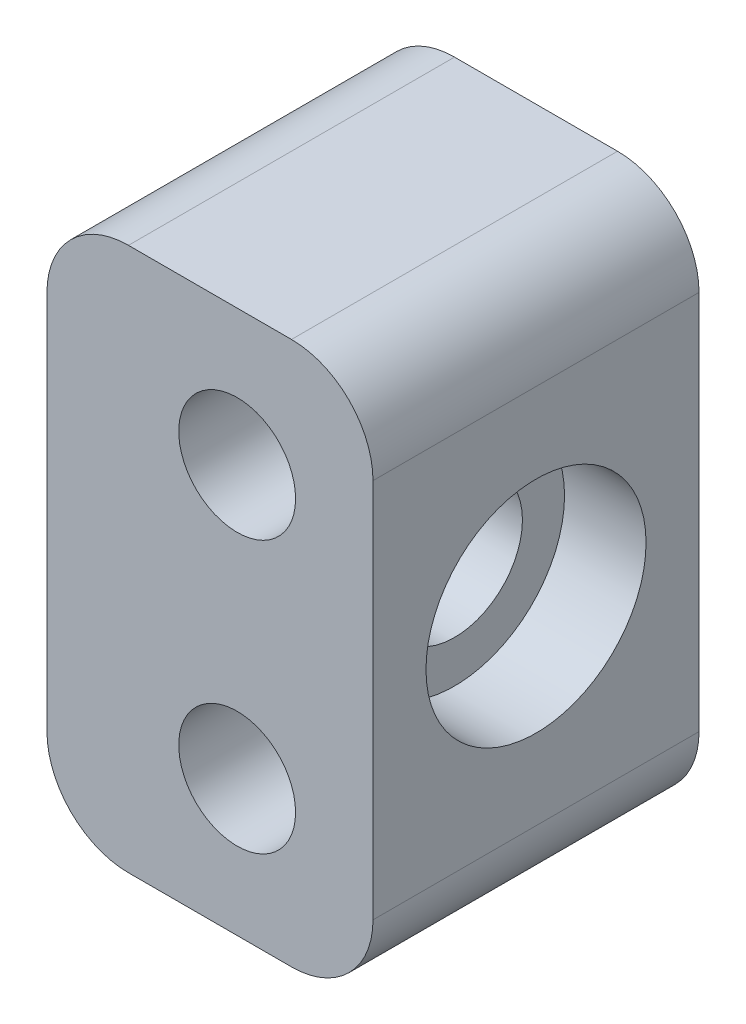
SolidWorks part; units mm, degrees
ref_plane "Front Plane" through (0, 0, 0) normal (0, 0, 1) x (1, 0, 0)
ref_plane "Top Plane" through (0, 0, 0) normal (0, 1, 0) x (1, 0, 0)
ref_plane "Right Plane" through (0, 0, 0) normal (1, 0, 0) x (0, 0, -1)
sketch "Sketch1" plane through (0, 0, 0) normal (0, 0, 1) x (1, 0, 0)
  line L0 (0, 5) -> (0, -5) construction
  line L5 (0, 5) -> (5, 5) construction
  line L6 (-4, -10) -> (2, -10)
  line L7 (-7, -7) -> (-7, 7)
  line L8 (-4, 10) -> (2, 10)
  line L9 (5, -7) -> (5, 7)
  line L10 (-7, -10) -> (5, 10) construction
  line L11 (-7, 10) -> (5, -10) construction
  line L12 (0, 5) -> (0, 10) construction
  circle A2 centre (0, 5) radius 2.15
  circle A3 centre (0, -5) radius 2.15
  arc A4 (-7, -7) -> (-4, -10) centre (-4, -7) ccw
  arc A5 (2, -10) -> (5, -7) centre (2, -7) ccw
  arc A6 (5, 7) -> (2, 10) centre (2, 7) ccw
  arc A7 (-4, 10) -> (-7, 7) centre (-4, 7) ccw
  point P0 (0, 0)
  point P10 (-1, 0)
  dimension "D2" = 10
  dimension "D3" = 4.3
  dimension "D4" = 4.3
  dimension "D6" = 3
  dimension "D1" = 12
  dimension "D5" = 20
extrude "Boss-Extrude1" add sketch "Sketch1" along normal blind 12
sketch "Sketch2" plane through (-7, 0, 0) normal (-1, 0, 0) x (0, 0, 1)
  line L0 (0, 0) -> (12, 0) construction
  line L3 (12, 7) -> (12, -7) construction
  line L10 (2.25, -3.75) -> (9.75, -3.75)
  line L11 (2.25, -3.75) -> (2.25, 3.75)
  line L12 (2.25, 3.75) -> (9.75, 3.75)
  line L13 (9.75, -3.75) -> (9.75, 3.75)
  line L14 (2.25, -3.75) -> (9.75, 3.75) construction
  line L15 (2.25, 3.75) -> (9.75, -3.75) construction
  line L16 (0, 7) -> (0, -7) construction
  circle A1 centre (6, 0) radius 2.5
  dimension "D2" = 5
  dimension "D1" = 7.5
extrude "Cut-Extrude1" cut sketch "Sketch2" against normal blind 5
extrude "Cut-Extrude2" cut sketch "Sketch2<2>" against normal through all contours A1 region at (-7, 0, 6)
sketch "Sketch2<2>" plane through (-7, 0, 0) normal (-1, 0, 0) x (0, 0, 1) same geometry as "Sketch2"
sketch "Sketch3" plane through (5, 0, 0) normal (1, 0, 0) x (0, 0, -1)
  circle A0 centre (-6, 0) radius 4.05
  dimension "D1" = 8.1
extrude "Cut-Extrude3" cut sketch "Sketch3" against normal blind 3
